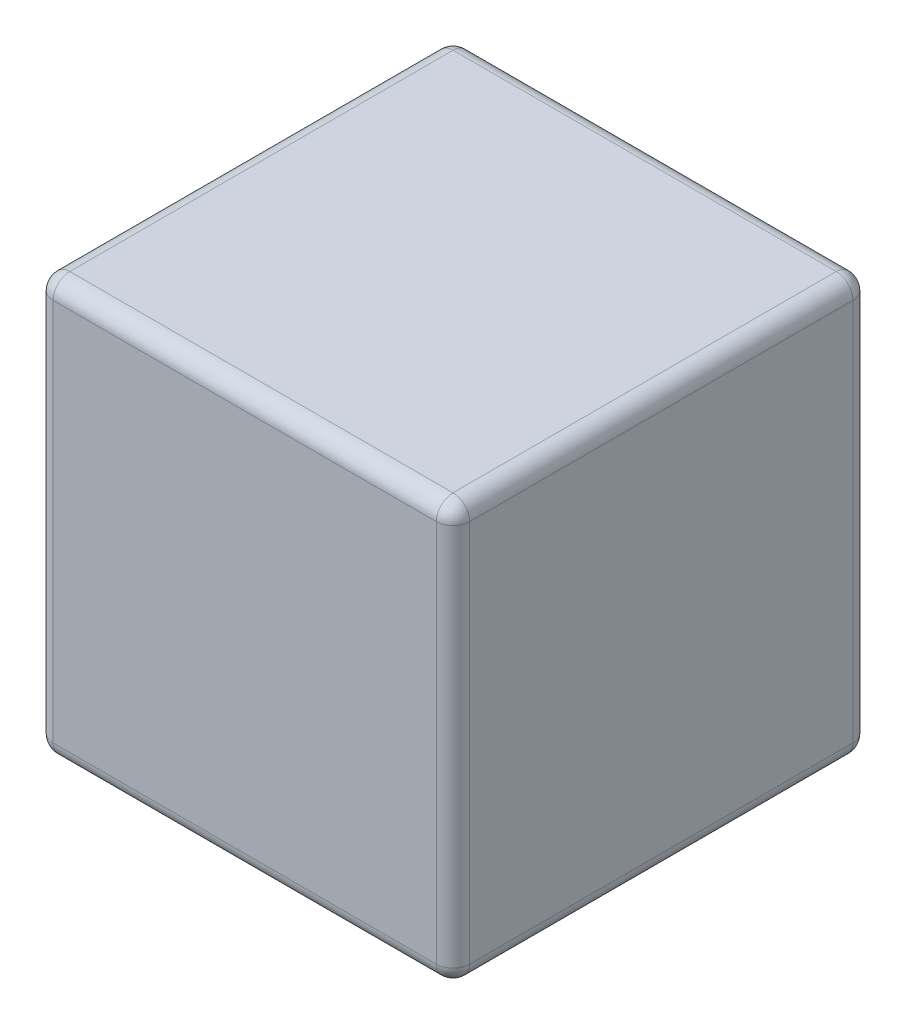
SolidWorks part; units mm, degrees
ref_plane "Front Plane" through (0, 0, 0) normal (0, 0, 1) x (1, 0, 0)
ref_plane "Top Plane" through (0, 0, 0) normal (0, 1, 0) x (1, 0, 0)
ref_plane "Right Plane" through (0, 0, 0) normal (1, 0, 0) x (0, 0, -1)
sketch "Sketch1" plane through (0, 0, 0) normal (0, 1, 0) x (1, 0, 0)
  line L1 (-125, -125) -> (125, -125)
  line L2 (-125, -125) -> (-125, 125)
  line L3 (-125, 125) -> (125, 125)
  line L4 (125, -125) -> (125, 125)
  line L5 (-125, -125) -> (125, 125) construction
  line L6 (-125, 125) -> (125, -125) construction
  point P0 (0, 0)
  dimension "D1" = 250
  dimension "D2" = 250
extrude "Boss-Extrude1" add sketch "Sketch1" along normal mid plane 250
fillet "Fillet1" radius 10 12 edges at (-125, 0, -125) (0, -125, -125) (-125, -125, 0) (125, 0, -125) (125, -125, 0) (-125, 0, 125) (125, 0, 125) (0, -125, 125) (0, 125, 125) (-125, 125, 0) (0, 125, -125) (125, 125, 0)
sketch "Sketch2" plane through (0, 0, -125) normal (0, 0, -1) x (-1, 0, 0)
  text T0 "LIFE SUPPORT" font "Century Gothic" height 25
extrude "Cut-Extrude1" cut sketch "Sketch2" against normal blind 15
